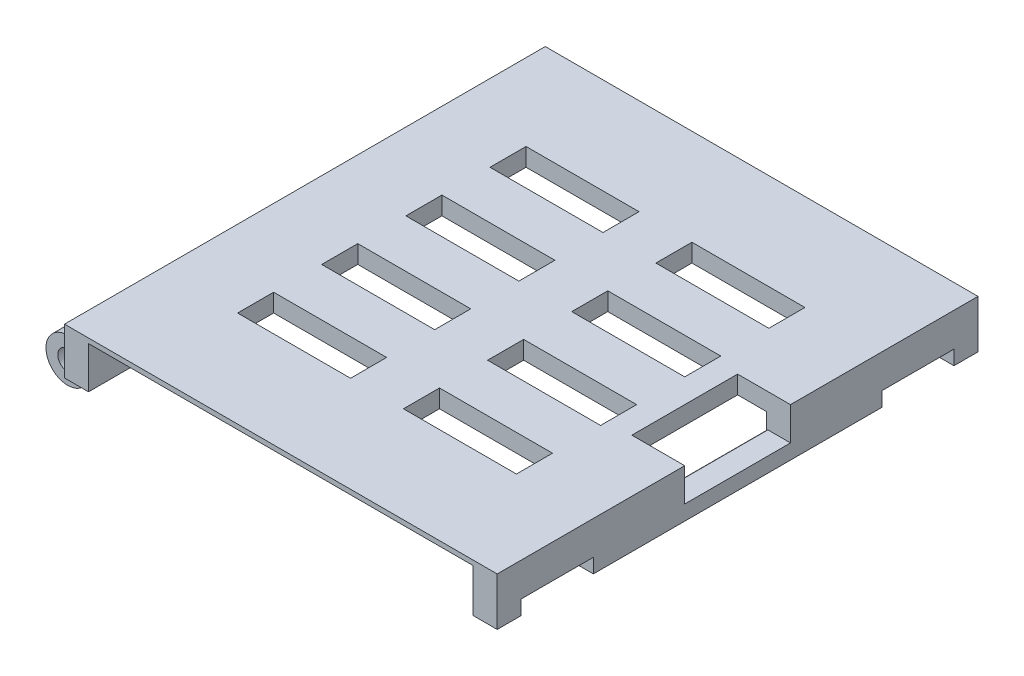
SolidWorks part; units mm, degrees
material "ABS"
ref_plane "Front Plane" through (0, 0, 0) normal (0, 0, 1) x (1, 0, 0)
ref_plane "Top Plane" through (0, 0, 0) normal (0, 1, 0) x (1, 0, 0)
ref_plane "Right Plane" through (0, 0, 0) normal (1, 0, 0) x (0, 0, -1)
sketch "Sketch1" plane through (0, 0, 0) normal (0, 0, 1) x (1, 0, 0)
  line L0 (28.575, 3.175) -> (27.9814, 2.6339) construction
  line L1 (-28.575, 0) -> (28.575, 0)
  line L2 (-28.575, 0) -> (-28.575, -6.35) construction
  line L3 (-28.575, -6.35) -> (28.575, -6.35) construction
  line L4 (28.575, 0) -> (28.575, -6.35) construction
  line L5 (-25.4, 0) -> (25.4, 0) construction
  line L6 (-25.4, 0) -> (-25.4, -3.9687) construction
  line L7 (-25.4, -3.9687) -> (25.4, -3.9687) construction
  line L8 (25.4, 0) -> (25.4, -3.9687) construction
  line L9 (-28.575, 0) -> (28.575, 0) construction
  line L10 (-28.575, 0) -> (-28.575, 6.35)
  line L11 (-28.575, 6.35) -> (28.575, 6.35)
  line L12 (28.575, 0) -> (28.575, 6.35)
  line L13 (-25.4, 0) -> (25.4, 0) construction
  line L14 (-25.4, 0) -> (-25.4, 3.9688)
  line L15 (-25.4, 3.9688) -> (25.4, 3.9688)
  line L16 (25.4, 0) -> (25.4, 3.9688)
  line L17 (28.575, -6.35) -> (30.1625, -6.35) construction
  line L18 (28.575, -6.35) -> (28.575, 3.175) construction
  line L19 (28.575, 3.175) -> (30.1625, 3.175) construction
  line L20 (30.1625, -6.35) -> (30.1625, 3.175) construction
  line L21 (28.067, 2.413) -> (28.575, 2.413) construction
  line L22 (27.94, 2.6791) -> (27.94, 3.0378) construction
  line L23 (28.067, 0) -> (28.067, -1.016) construction
  line L24 (-28.575, -6.35) -> (-32.3558, -1.6248) construction
  line L25 (-31.575, 0) -> (-28.575, 0) construction
  line L26 (-30.575, -1) -> (-28.575, -1) construction
  line L27 (-28.575, 6.35) -> (-30.2575, -1)
  line L28 (28.575, 3.2385) -> (25.4, 3.2385)
  line L29 (28.575, 3.2385) -> (28.575, 1.9685)
  line L30 (28.575, 1.9685) -> (25.4, 1.9685)
  line L31 (25.4, 3.2385) -> (25.4, 1.9685)
  line L32 (-31.7362, 0.3076) -> (-31.9265, 1.8514)
  line L33 (-28.7191, -1.3134) -> (-28.575, 0)
  line L34 (-28.702, -1) -> (-28.575, -1) construction
  line L35 (-31.7362, 0.3076) -> (-29.9582, 0.3076) construction
  line L40 (28.575, 3.2385) -> (21.59, 3.2385)
  line L41 (28.575, 3.2385) -> (28.575, 6.35)
  line L42 (28.575, 6.35) -> (21.59, 6.35)
  line L43 (21.59, 3.2385) -> (21.59, 6.35)
  line L44 (-31.7362, 0.3076) -> (-31.575, -1) construction
  arc A0 (27.9814, 2.6339) -> (28.067, 2.413) centre (28.067, 2.54) ccw construction
  arc A1 (28.067, -1.016) -> (28.575, -1.016) centre (28.321, -1.016) ccw construction
  arc A2 (-32.3558, -1.6248) -> (-31.575, 0) centre (-31.575, -1) cw construction
  circle A3 centre (-31.575, -1) radius 1 construction
  circle A4 centre (-31.575, -1) radius 1.3175
  arc A5 (-31.9265, 1.8514) -> (-28.7191, -1.3134) centre (-31.575, -1) ccw
  circle A6 centre (-31.575, -1) radius 2.873 construction
  point P44 (0, 3.9687)
  point P45 (0, 6.35)
  point P48 (0, 0)
  dimension "D4" = 2
  dimension "D13" = 0.254
  dimension "D15" = 0.127
  dimension "D1" = 7.9375
  dimension "D2" = 12.7
  dimension "D3" = 2
  dimension "D5" = 57.15
  dimension "D6" = 50.8
  dimension "D7" = 3.175
  dimension "D8" = 0.4445
  dimension "D9" = 0.127
  dimension "D10" = 2.413
  dimension "D11" = 0.635
  dimension "D12" = 0.762
  dimension "D14" = 1.5875
  dimension "D17" = 0.127
  dimension "D18" = 3.81
  dimension "D19" = 1.778
  dimension "D16" = 0.3175
extrude "Boss-Extrude1" add sketch "Sketch1" along normal mid plane 63.5 contours L15 L43 L11 L10 L1 L14 | L32 A5 L33 L10 L27 A4 | L43 L15 L16 L28 L12 L11 | L30 L12 L28 L16 | L12 L30 L16 L1 region at (-5.7344, 4.8564, 0) region at (-28.7643, -0.6439, 0) region at (26.9875, 0.9842, 0) region at (25.3156, 4.969, 0) region at (26.9875, 2.6035, 0)
extrude "Cut-Extrude1" cut sketch "Sketch1<4>" against normal mid plane 13.97 contours L28 L31 L30 L12 | L16 L28 L12 L11 region at (25.3156, 4.969, 0) region at (26.9875, 2.6035, 0)
sketch "Sketch1<4>" plane through (0, 0, 0) normal (0, 0, 1) x (1, 0, 0) same geometry as "Sketch1"
ref_plane "Plane1" through (-28.575, 0, 0) normal (1, 0, 0) x (0, 0, -1)
sketch "Sketch2" plane through (-28.575, 9.605, 0) normal (-1, 0, 0) x (0, 0, 1)
  line L0 (31.75, -3.255) -> (-31.75, -3.255) construction
  line L2 (31.75, -13.478) -> (28.321, -13.478)
  line L3 (31.75, -13.478) -> (31.75, -3.255)
  line L4 (31.75, -3.255) -> (28.321, -3.255)
  line L5 (28.321, -13.478) -> (28.321, -3.255)
  line L6 (31.75, -3.255) -> (-31.75, -3.255) construction
  line L8 (-31.75, -13.478) -> (-28.321, -13.478)
  line L9 (-31.75, -13.478) -> (-31.75, -3.255)
  line L10 (-31.75, -3.255) -> (-28.321, -3.255)
  line L11 (-28.321, -13.478) -> (-28.321, -3.255)
  line L13 (-31.75, -13.478) -> (31.75, -13.478) construction
  line L14 (31.75, -3.255) -> (6.985, -3.255) construction
  line L15 (-1.7145, -13.478) -> (1.7145, -13.478)
  line L16 (-1.7145, -13.478) -> (-1.7145, -3.255)
  line L17 (-1.7145, -3.255) -> (1.7145, -3.255)
  line L18 (1.7145, -13.478) -> (1.7145, -3.255)
  line L27 (-8.0645, -13.478) -> (8.0645, -13.478)
  line L28 (-8.0645, -13.478) -> (-8.0645, -3.255)
  line L29 (-8.0645, -3.255) -> (8.0645, -3.255)
  line L30 (8.0645, -13.478) -> (8.0645, -3.255)
  line L36 (-31.75, -7.7536) -> (-31.75, -13.478) construction
  line L41 (-21.971, -13.478) -> (21.971, -13.478)
  line L42 (-21.971, -13.478) -> (-21.971, -3.255)
  line L43 (-21.971, -3.255) -> (21.971, -3.255)
  line L44 (21.971, -13.478) -> (21.971, -3.255)
  point P20 (0, -3.255)
  point P25 (0, -3.255)
  point P32 (0, -13.478)
  point P33 (0, -13.478)
  point P38 (0, -13.478)
  dimension "D1" = 3.429
  dimension "D2" = 6.35
  dimension "D3" = 6.35
extrude "Cut-Extrude2" cut sketch "Sketch2" along normal blind 19.05 contours L11 L8 L9 L10 | L42 L43 L28 L41 | L28 L29 L16 L27 | L30 L27 L18 L29 | L44 L41 L30 L43 | L2 L5 L4 L3 | L18 L15 L16 L17 region at (-28.575, 1.2385, 30.0355) region at (-28.575, 1.2385, -30.0355) region at (-28.575, 1.2385, 0) region at (-28.575, 1.2385, -4.8895) region at (-28.575, 1.2385, 4.8895) region at (-28.575, 1.2385, -15.0177) region at (-28.575, 1.2385, 15.0178)
sketch "Sketch3" plane through (0, 6.35, 0) normal (0, 1, 0) x (1, 0, 0)
  line L1 (28.575, 31.75) -> (-34.448, 31.75)
  line L2 (28.575, 31.75) -> (28.575, 8.0645)
  line L3 (28.575, 8.0645) -> (-34.448, 8.0645)
  line L4 (-34.448, 31.75) -> (-34.448, 8.0645)
  line L5 (28.575, -31.75) -> (-34.448, -31.75)
  line L6 (28.575, -31.75) -> (28.575, -8.0645)
  line L7 (28.575, -8.0645) -> (-34.448, -8.0645)
  line L8 (-34.448, -31.75) -> (-34.448, -8.0645)
extrude "Cut-Extrude3" [suppressed] cut sketch "Sketch3" against normal through all
sketch "Sketch4" plane through (0, 3.9688, 0) normal (0, -1, 0) x (1, 0, 0)
  line L0 (-10.9537, 14.2875) -> (-10.9537, 7.9375) construction
  line L1 (-18.415, 19.05) -> (-3.4925, 19.05)
  line L2 (-18.415, 19.05) -> (-18.415, 14.2875)
  line L3 (-18.415, 14.2875) -> (-3.4925, 14.2875)
  line L4 (-3.4925, 19.05) -> (-3.4925, 14.2875)
  line L5 (3.4925, 19.05) -> (18.415, 19.05)
  line L6 (3.4925, 19.05) -> (3.4925, 14.2875)
  line L7 (3.4925, 14.2875) -> (18.415, 14.2875)
  line L8 (18.415, 19.05) -> (18.415, 14.2875)
  line L9 (-18.415, 7.9375) -> (-3.4925, 7.9375)
  line L10 (-18.415, 7.9375) -> (-18.415, 3.175)
  line L11 (-18.415, 3.175) -> (-3.4925, 3.175)
  line L12 (-3.4925, 7.9375) -> (-3.4925, 3.175)
  line L13 (3.4925, 7.9375) -> (18.415, 7.9375)
  line L14 (3.4925, 7.9375) -> (3.4925, 3.175)
  line L15 (3.4925, 3.175) -> (18.415, 3.175)
  line L16 (18.415, 7.9375) -> (18.415, 3.175)
  line L17 (-18.415, -3.175) -> (-3.4925, -3.175)
  line L18 (-18.415, -3.175) -> (-18.415, -7.9375)
  line L19 (-18.415, -7.9375) -> (-3.4925, -7.9375)
  line L20 (-3.4925, -3.175) -> (-3.4925, -7.9375)
  line L21 (3.4925, -3.175) -> (18.415, -3.175)
  line L22 (3.4925, -3.175) -> (3.4925, -7.9375)
  line L23 (3.4925, -7.9375) -> (18.415, -7.9375)
  line L24 (18.415, -3.175) -> (18.415, -7.9375)
  line L25 (-18.415, -14.2875) -> (-3.4925, -14.2875)
  line L26 (-18.415, -14.2875) -> (-18.415, -19.05)
  line L27 (-18.415, -19.05) -> (-3.4925, -19.05)
  line L28 (-3.4925, -14.2875) -> (-3.4925, -19.05)
  line L29 (3.4925, -14.2875) -> (18.415, -14.2875)
  line L30 (3.4925, -14.2875) -> (3.4925, -19.05)
  line L31 (3.4925, -19.05) -> (18.415, -19.05)
  line L32 (18.415, -14.2875) -> (18.415, -19.05)
  line L33 (-10.9537, 3.175) -> (-10.9537, -3.175) construction
  line L34 (-10.9537, -7.9375) -> (-10.9537, -14.2875) construction
  line L35 (10.9537, -7.9375) -> (10.9537, -14.2875) construction
  line L36 (10.9537, 3.175) -> (10.9537, -3.175) construction
  line L37 (10.9537, 14.2875) -> (10.9537, 7.9375) construction
  line L38 (-3.4925, 16.6687) -> (3.4925, 16.6687) construction
  line L39 (-25.4, 31.75) -> (25.4, 31.75) construction
  line L40 (-25.4, 31.75) -> (-25.4, -31.75) construction
  point P44 (0, 16.6687)
  point P49 (0, 31.75)
  point P52 (-10.9537, 0)
  dimension "D1" = 6.985
  dimension "D2" = 6.985
  dimension "D3" = 12.7
  dimension "D4" = 6.35
extrude "Cut-Extrude4" cut sketch "Sketch4" against normal through all
fillet "Fillet1" [suppressed] radius 2.032
sketch "Sketch6" plane through (0, 6.35, 0) normal (0, 1, 0) x (1, 0, 0)
  line L0 (-25.4, -31.75) -> (-25.4, 31.75) construction
  line L1 (28.575, -31.75) -> (-36.5496, -31.75)
  line L2 (28.575, -31.75) -> (28.575, 31.75)
  line L3 (28.575, 31.75) -> (-36.5496, 31.75)
  line L4 (-36.5496, -31.75) -> (-36.5496, 31.75)
  line L13 (28.575, 31.75) -> (-25.4, 31.75)
  line L14 (28.575, 31.75) -> (28.575, 8.985)
  line L15 (28.575, 8.985) -> (-25.4, 8.985)
  line L16 (-25.4, 31.75) -> (-25.4, 8.985)
  line L17 (-25.4, -31.75) -> (-25.4, 31.75) construction
  line L18 (28.575, -31.75) -> (-25.4, -31.75)
  line L19 (28.575, -31.75) -> (28.575, -8.985)
  line L20 (28.575, -8.985) -> (-25.4, -8.985)
  line L21 (-25.4, -31.75) -> (-25.4, -8.985)
  line L22 (21.59, -6.985) -> (25.4, -6.985) construction
  line L23 (-34.448, -21.971) -> (-34.448, -28.321) construction
  line L24 (-25.4, 31.75) -> (-34.448, 31.75)
  line L25 (-25.4, 31.75) -> (-25.4, 28.321)
  line L26 (-25.4, 28.321) -> (-34.448, 28.321)
  line L27 (-34.448, 31.75) -> (-34.448, 28.321)
  line L28 (-25.4, -31.75) -> (-34.448, -31.75)
  line L29 (-25.4, -31.75) -> (-25.4, -28.321)
  line L30 (-25.4, -28.321) -> (-34.448, -28.321)
  line L32 (-34.448, -28.321) -> (-34.448, -31.75)
  line L33 (-34.448, -28.321) -> (-28.7191, -28.321) construction
  dimension "D1" = 2
extrude "Cut-Extrude6" [suppressed] cut sketch "Sketch6" against normal through all
sketch "Sketch8" plane through (0, 0, 0) normal (0, 0, 1) x (1, 0, 0)
  line L0 (25.4, 0) -> (28.575, 0) construction
  line L1 (25.4, 0) -> (25.4, 3.9688) construction
  line L2 (25.4, 2.032) -> (25.4, 0)
  line L3 (25.4, 0) -> (27.432, 0)
  arc A0 (25.4, 2.032) -> (27.432, 0) centre (27.432, 2.032) ccw
  circle A1 centre (28.418, 3.018) radius 3.175
  dimension "D1" = 4.064
  dimension "D2" = 6.35
extrude "Cut-Extrude7" cut sketch "Sketch8" against normal mid plane 13.97 contours A0 | A0 L2 L3 region at (25.8539, 0.4539, 0) region at (26.1505, 0.7505, 0)
sketch "Sketch9" plane through (0, 0, 31.75) normal (0, 0, 1) x (1, 0, 0)
  line L0 (-4.3329, -0.635) -> (4.3329, -0.635) construction
  line L1 (-25.4, 3.9688) -> (25.4, 3.9688)
  line L2 (-25.4, 3.9688) -> (-25.4, 5.715)
  line L3 (-25.4, 5.715) -> (25.4, 5.715)
  line L4 (25.4, 3.9688) -> (25.4, 5.715)
  line L5 (-25.4, -3.9687) -> (25.4, -3.9687) construction
  line L6 (-25.4, -3.9687) -> (-25.4, -5.715) construction
  line L7 (-25.4, -5.715) -> (25.4, -5.715) construction
  line L8 (25.4, -3.9687) -> (25.4, -5.715) construction
  point P5 (0, -0.635)
  dimension "D1" = 5.08
  dimension "D2" = 6.35
extrude "Cut-Extrude8" cut sketch "Sketch9" against normal blind 6.35
mirror "Mirror1" about plane through (0, 0, 0) normal (0, 0, 1) of "Cut-Extrude8"
sketch "Sketch10" plane through (28.575, 0, 0) normal (1, 0, 0) x (0, 0, -1)
  line L0 (-31.75, 0) -> (31.75, 0) construction
  line L1 (19.05, 0) -> (28.575, 0)
  line L2 (19.05, 0) -> (19.05, 1.905)
  line L3 (19.05, 1.905) -> (28.575, 1.905)
  line L4 (28.575, 0) -> (28.575, 1.905)
  line L5 (31.75, 0) -> (31.75, 6.35) construction
  line L6 (19.05, 0.9525) -> (-19.05, 0.9525) construction
  line L7 (-19.05, 0) -> (-28.575, 0)
  line L8 (-19.05, 0) -> (-19.05, 1.905)
  line L9 (-19.05, 1.905) -> (-28.575, 1.905)
  line L10 (-28.575, 0) -> (-28.575, 1.905)
  point P16 (0, 0.9525)
  dimension "D1" = 9.525
  dimension "D2" = 1.905
  dimension "D3" = 3.175
extrude "Cut-Extrude9" cut sketch "Sketch10" against normal blind 1.905
sketch "Sketch11" plane through (0, 0, 31.75) normal (0, 0, 1) x (1, 0, 0)
  line L0 (-28.575, 0) -> (-28.575, 6.35) construction
  line L1 (-25.4, 0) -> (-28.575, 0)
  line L2 (-25.4, 0) -> (-25.4, 0.1905)
  line L3 (-25.4, 0.1905) -> (-28.575, 0.1905)
  line L4 (-28.575, 0) -> (-28.575, 0.1905)
  dimension "D1" = 0.1905
extrude "Cut-Extrude10" cut sketch "Sketch11" against normal through all
fillet "Fillet2" radius 0.127 1 edges at (25.4215, 1.9685, 0)
